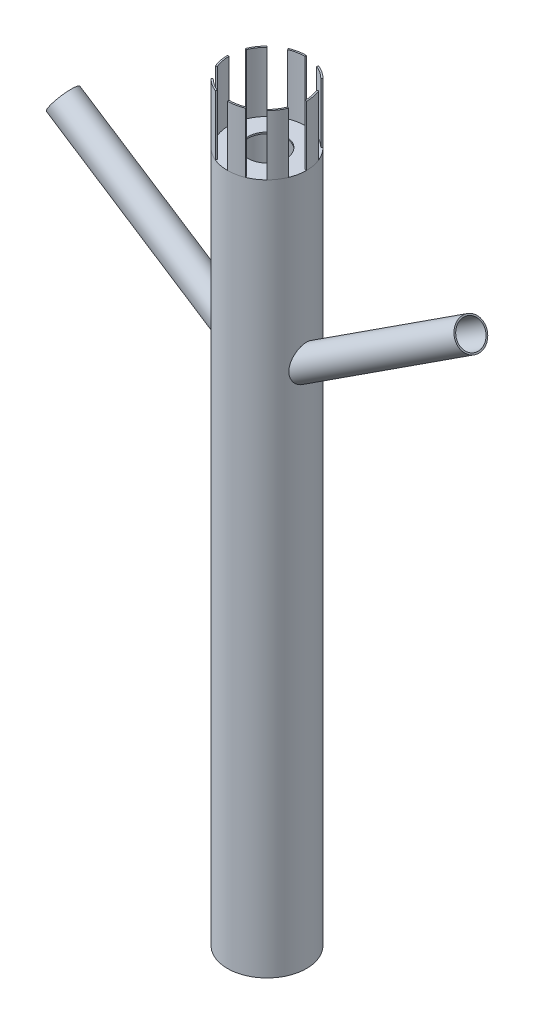
SolidWorks part; units mm, degrees
ref_plane "Front Plane" through (0, 0, 0) normal (0, 0, 1) x (1, 0, 0)
ref_plane "Top Plane" through (0, 0, 0) normal (0, 1, 0) x (1, 0, 0)
ref_plane "Right Plane" through (0, 0, 0) normal (1, 0, 0) x (0, 0, -1)
sketch "connectorpiece" plane through (0, 0, 0) normal (0, 1, 0) x (1, 0, 0)
  line L0 (0, 0) -> (-26, 0) construction
  circle A0 centre (0, 0) radius 26
  circle A1 centre (0, 0) radius 25
  circle A2 centre (0, 0) radius 22
  dimension "D1" = 1
  dimension "D2" = 50
  dimension "D3" = 3
extrude "velcro connection" add sketch "connectorpiece" along normal blind 39.3909 contours A1 A2 region at (-24.2929, 0, 0)
extrude "fabric" add sketch "connectorpiece<6>" along normal blind 453.9726 separate body contours A0 A1 region at (-25.2646, 0, 0)
sketch "connectorpiece<6>" plane through (0, 0, 0) normal (0, 1, 0) x (1, 0, 0) same geometry as "connectorpiece"
sketch "Sketch2" plane through (0, 453.9726, 0) normal (0, 1, 0) x (1, 0, 0)
  circle A0 centre (0, 0) radius 12.5
  circle A1 centre (0, 0) radius 26
  circle M1 centre (0, 0) radius 25
  dimension "D1" = 25
  dimension "D2" = 52
extrude "top hole" add sketch "Sketch2" against normal blind 1 contours A0 M1 region at (-24.2929, 453.9726, 0)
sketch "arm points" plane through (0, 0, 0) normal (0, 0, 1) x (1, 0, 0)
  line L0 (0, 0) -> (0, 344.7138)
  line L1 (0, 344.7138) -> (-26, 344.7138)
  line L2 (-26, 453.9726) -> (-26, 0) construction
  line L3 (0, 0) -> (-26, 0) construction
  line L4 (0, 344.7138) -> (26, 344.7138)
  line L5 (26, 0) -> (26, 453.9726) construction
  line L6 (26, 344.7138) -> (133.8922, 414.7798)
  line L7 (-26, 344.7138) -> (-133.8922, 414.7798)
  dimension "D1" = 344.7138
  dimension "D2" = 128.6466
  dimension "D3" = 57
  dimension "D4" = 128.6466
  dimension "D5" = 57
sketch3d "armplane1"
  line L0 (-26, 344.7138, 0) -> (-133.8922, 414.7798, 0) construction
sketch3d "armplane2"
  line L0 (26, 344.7138, 0) -> (133.8922, 414.7798, 0) construction
sketch "arm 1" plane through (-283.6356, 184.1951, 0) normal (0.8387, -0.5446, 0) x (0, 0, -1)
  circle A0 centre (0, 274.9407) radius 8.7519
  circle A1 centre (0, 274.9407) radius 9.7519
  dimension "D1" = 19.5037
  dimension "D2" = 17.5037
extrude "arm 1 extrusion" add sketch "arm 1" along normal up to surface (124.1555 mm away) up to face at (0, 0, 25)
sketch "Sketch4" plane through (283.6356, 184.1951, 0) normal (-0.8387, -0.5446, 0) x (0, 0, 1)
  circle A0 centre (0, 274.9407) radius 9.7519
  circle A1 centre (0, 274.9407) radius 8.7519
  dimension "D1" = 19.5037
  dimension "D2" = 17.5037
extrude "Boss-Extrude2" add sketch "Sketch4" along normal up to surface (134.9796 mm away) separate body up to face at (0, 453.9726, 26)
sketch "Sketch5" plane through (0, 453.9726, 0) normal (0, 1, 0) x (1, 0, 0)
  line L0 (0, 0) -> (26, 0)
  line L1 (0, 0) -> (24.0209, -9.9498)
  line L2 (0, 0) -> (18.3848, -18.3848)
  line L3 (0, 0) -> (9.9498, -24.0209)
  line L5 (0, 0) -> (0, -26)
  line L6 (0, 0) -> (-9.9498, -24.0209)
  line L7 (0, 0) -> (-18.3848, -18.3848)
  line L8 (0, 0) -> (-24.0209, -9.9498)
  line L9 (0, 0) -> (-26, 0)
  line L11 (0, 0) -> (-24.0209, 9.9498)
  line L12 (0, 0) -> (-18.3848, 18.3848)
  line L13 (0, 0) -> (-9.9498, 24.0209)
  line L14 (0, 0) -> (0, 26)
  line L15 (0, 0) -> (9.9498, 24.0209)
  line L16 (0, 0) -> (18.3848, 18.3848)
  line L17 (0, 0) -> (24.0209, 9.9498)
  line L18 (0, 0) -> (26, 0) construction
  circle A0 centre (0, 0) radius 26
  circle A1 centre (0, 0) radius 25
  circle A2 centre (0, 0) radius 26 construction
  circle M1 centre (0, 0) radius 26
  dimension "D1" = 1
  dimension "D2" = 16
extrude "Boss-Extrude4" add sketch "Sketch5" along normal blind 39.3909 separate body contours A1 L9 L8 M1 | A1 L7 L6 M1 | A1 L5 L3 M1 | A1 L2 L1 M1 | A1 L0 L17 M1 | A1 L16 L15 M1 | A1 L14 L13 M1 | A1 L12 L11 M1 region at (24.8528, 453.9726, -4.9435) region at (21.0692, 453.9726, 14.078) region at (4.9435, 453.9726, 24.8528) region at (-14.078, 453.9726, 21.0692) region at (-24.8528, 453.9726, 4.9435) region at (-21.0692, 453.9726, -14.078) region at (-4.9435, 453.9726, -24.8528) region at (14.078, 453.9726, -21.0692)
equation "\"D\"= 50mm"
equation "\"D2@connectorpiece\"=\"D\""
equation "\"D1@velcro connection\" = \"lt\""
equation "\"D1@fabric\" = \"lb\" - \"lt\""
equation "\"fabdiam\"= 1mm"
equation "\"D1@connectorpiece\"=\"fabdiam\""
equation "\"D1@Sketch2\"=\"D\"/2"
equation "\"D2@Sketch2\"=\"D\"+2*\"fabdiam\""
equation "\"D1@top hole\"= \"fabdiam\""
equation "\"truedb\"= .3089m"
equation "\"scale\"= \"D\" / \"truedb\""
equation "\"velcrodiam\"= 3mm"
equation "\"lt\"= 0.243357m * \"scale\""
equation "\"larm\"= 0.794779m * \"scale\""
equation "\"ltorso\"= 1.93995m * \"scale\""
equation "\"lb\"= 3.048m * \"scale\""
equation "\"darm\"= 0.120494m * \"scale\""
equation "\"db\"= 0.308942m * \"scale\""
equation "\"lconn\"= 0.129445m * \"scale\""
equation "\"ang\"= 57deg"
equation "\"D1@arm points\"=\"lconn\"+\"ltorso\"+\"darm\"/2"
equation "\"D2@arm points\"=\"larm\""
equation "\"D3@arm points\"=\"ang\""
equation "\"D4@arm points\"=\"larm\""
equation "\"D5@arm points\"=\"ang\""
equation "\"D1@arm 1\"=\"darm\""
equation "\"D2@arm 1\"=\"darm\"-2*\"fabdiam\""
equation "\"D1@Sketch4\"=\"darm\""
equation "\"D2@Sketch4\"=\"darm\"-\"fabdiam\"*2"
equation "\"D1@Sketch5\"=\"fabdiam\""
equation "\"D1@Boss-Extrude4\"=\"lt\""
